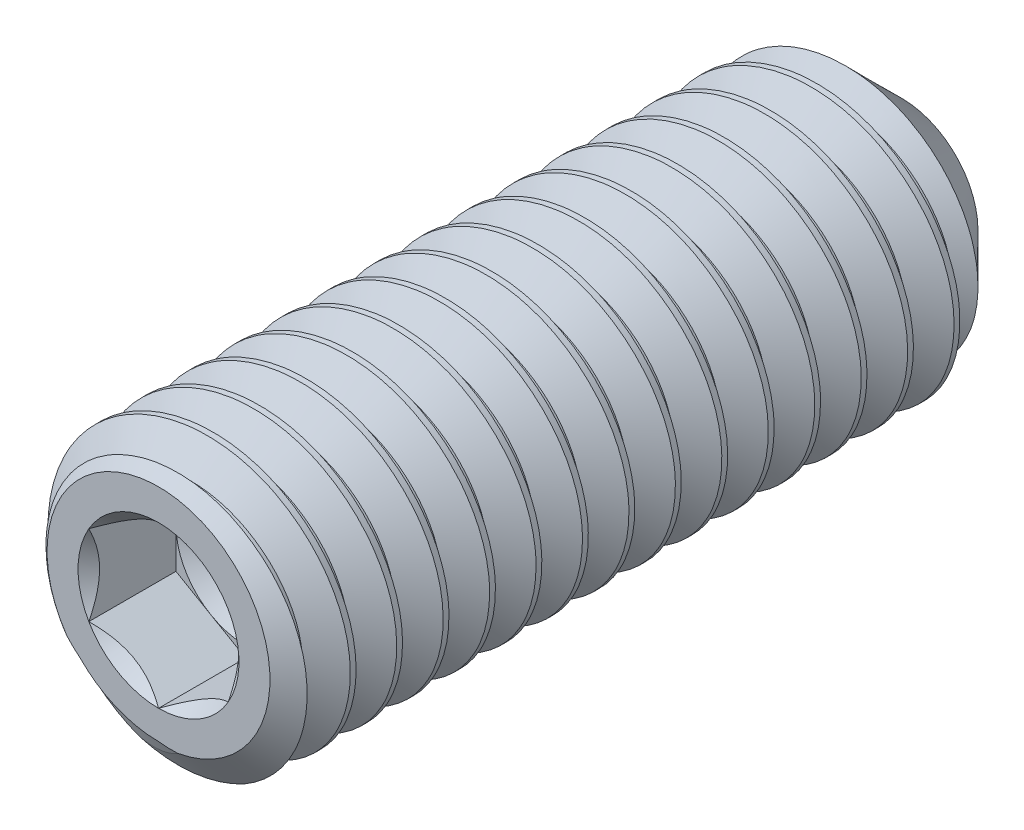
SolidWorks part; units mm, degrees
ref_plane "Front" through (0, 0, 0) normal (0, 0, 1) x (1, 0, 0)
ref_plane "Top" through (0, 0, 0) normal (0, 1, 0) x (1, 0, 0)
ref_plane "Right" through (0, 0, 0) normal (1, 0, 0) x (0, 0, -1)
sketch "Sketch22" plane through (0, 0, 0) normal (1, 0, 0) x (0, 0, -1)
  line L0 (-3.7531, 0) -> (-3.7531, 1.2)
  line L1 (-3.7531, 1.2) -> (-3.543, 1.5)
  line L2 (-3.543, 1.5) -> (3.5689, 1.5)
  line L3 (3.5689, 1.5) -> (4.2469, 0.8219)
  line L4 (4.2469, 0.8219) -> (3.7531, 0)
  line L5 (3.7531, 0) -> (-3.7531, 0)
  line L6 (3.7531, 0) -> (4.2469, 0) construction
  line L7 (4.2469, 0) -> (4.2469, 0.8219) construction
  line L8 (4.2469, -0.8219) -> (3.7531, 0) construction
  line L9 (-3.543, -1.5) -> (3.5689, -1.5) construction
  dimension "Dia" = 3
  dimension "Length" = 8
  dimension "D3" = 35
  dimension "D5" = 118
  dimension "D6" = 45
  dimension "D7" = 2.4
revolve "Revolve1" add sketch "Sketch22" angle 360 about L6
ref_plane "Plane1" through (0, 0, -4.2469) normal (0, 0, 1) x (1, 0, 0)
sketch "Sketch27" plane through (0, 0, -4.2469) normal (0, 0, 1) x (1, 0, 0)
  circle A0 centre (0, 0) radius 1.5 construction
  circle A1 centre (0, 0) radius 1.5
curve "Helix/Spiral1" pitch 0.5 height 8.5 turns 17
sketch "Sketch28" plane through (0, 0, 0) normal (1, 0, 0) x (0, 0, -1)
  line L0 (4.2469, 1.5) -> (4.6844, 1.5)
  line L1 (4.6844, 1.5) -> (4.4969, 1.1752)
  line L2 (4.4969, 1.1752) -> (4.4344, 1.1752)
  line L3 (4.4344, 1.1752) -> (4.2469, 1.5)
  line L4 (4.3407, 1.3376) -> (4.5907, 1.3376) construction
  line L6 (-3.543, 1.5) -> (3.5689, 1.5) construction
  dimension "D1" = 0.0625
  dimension "D3" = 60
  dimension "D2" = 0.25
sweep "Cut-Sweep2" cut profiles "Sketch28" path "Helix/Spiral1"
sketch "Sketch23" plane through (0, 0, 3.7531) normal (0, 0, 1) x (1, 0, 0)
  line L1 (0, 0.866) -> (-0.75, 0.433)
  line L2 (-0.75, 0.433) -> (-0.75, -0.433)
  line L3 (-0.75, -0.433) -> (0, -0.866)
  line L4 (0, -0.866) -> (0.75, -0.433)
  line L5 (0.75, -0.433) -> (0.75, 0.433)
  line L6 (0.75, 0.433) -> (0, 0.866)
  circle A0 centre (0, 0) radius 0.75 construction
  dimension "Hex" = 1.5
extrude "Cut-Extrude10" cut sketch "Sketch23" against normal blind 0.9375
sketch "Sketch24" plane through (0, 0, 3.7531) normal (0, 0, 1) x (1, 0, 0)
  circle A0 centre (0, 0) radius 0.866
extrude "Cut-Extrude11" cut sketch "Sketch24" against normal through all draft 45
sketch "Sketch26" plane through (0, 0, 2.8156) normal (0, 0, 1) x (1, 0, 0)
  circle A0 centre (0, 0) radius 0.75 construction
  circle A1 centre (0, 0) radius 0.75
extrude "Cut-Extrude12" cut sketch "Sketch26" against normal through all draft 60
sketch "Sketch30" plane through (0, 0, 0) normal (1, 0, 0) x (0, 0, -1)
  line L0 (-3.543, 1.5) -> (3.5689, 1.5) construction
  line L1 (-3.7531, 0) -> (-3.7531, 1.2) construction
  line L2 (4.2469, 0) -> (4.2469, 0.8219) construction
  line L3 (-3.543, -1.5) -> (3.5689, -1.5) construction
  point P0 (-3.7531, 1.5)
  point P1 (4.2469, 1.5)
  point P2 (4.2469, -1.5)
  point P11 (3.4969, -1.5)
  dimension "D1" = 0.75
sketch "Sketch31" plane through (0, 0, 0) normal (1, 0, 0) x (0, 0, -1)
  line L2 (3.7531, 0) -> (4.2469, -0.8219)
  line L3 (4.2469, 0.8219) -> (3.7531, 0)
equation "\"D7@Sketch22\"=\"Dia@Sketch22\"*.8"
equation "\"D1@Sketch28\" = \"D4@Helix/Spiral1\" * .125"
equation "\"D2@Sketch28\" = \"D4@Helix/Spiral1\" * .5"
equation "\"D3@Helix/Spiral1\" = \"Length@Sketch22\" + \"D4@Helix/Spiral1\""
equation "\"D1@Sketch30\" = \"D4@Helix/Spiral1\" * 1.5"
equation "\"hex Depth@Cut-Extrude10\" = \"Hex@Sketch23\" * .625"
